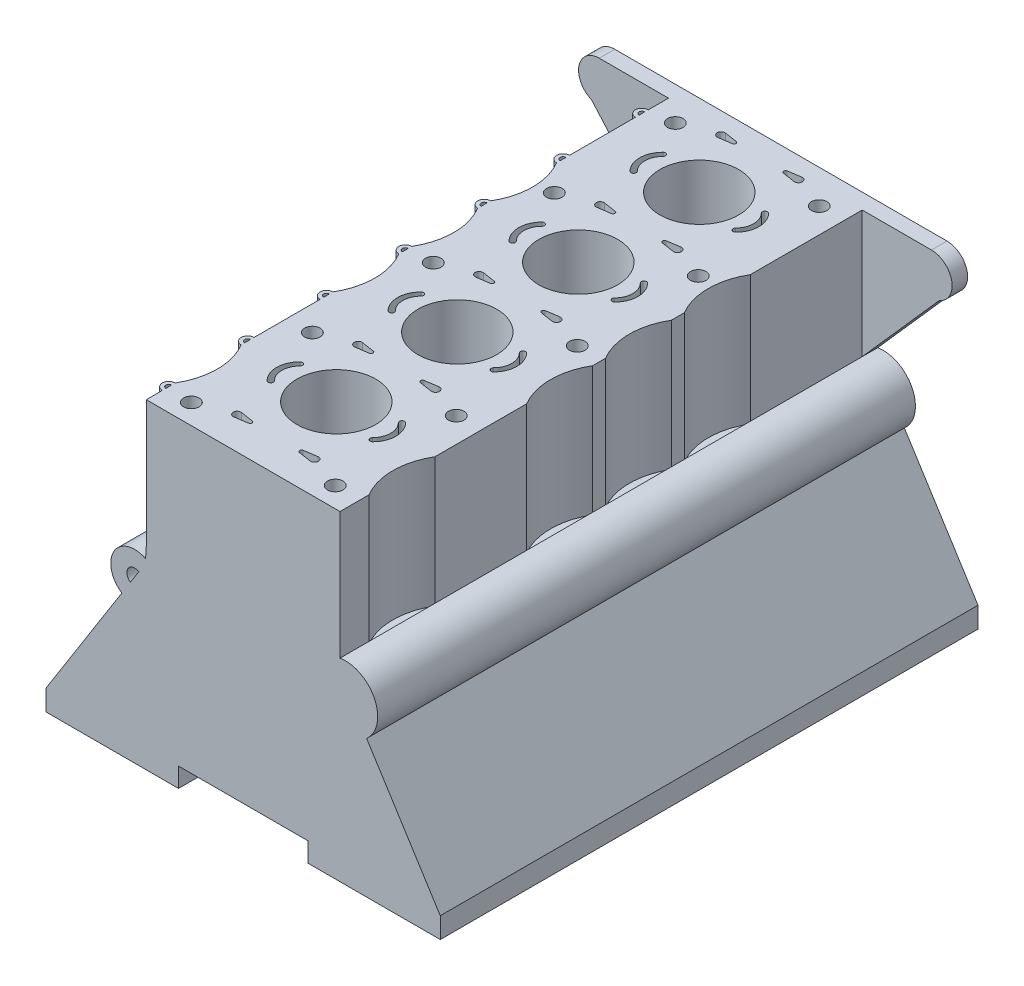
SolidWorks part; units mm, degrees
ref_plane "Front Plane" through (0, 0, 0) normal (0, 0, 1) x (1, 0, 0)
ref_plane "Top Plane" through (0, 0, 0) normal (0, 1, 0) x (1, 0, 0)
ref_plane "Right Plane" through (0, 0, 0) normal (1, 0, 0) x (0, 0, -1)
sketch "Sketch1" plane through (0, 0, 0) normal (0, 0, 1) x (1, 0, 0)
  line L0 (0, 162.6607) -> (0, -85.2855) construction
  line L1 (128.5, 162.6607) -> (-128.5, 162.6607)
  line L2 (-134.5607, 131.853) -> (-74.9405, 64.4333)
  line L3 (134.5607, 131.853) -> (74.9405, 64.4333)
  line L4 (-74.9405, 64.4333) -> (-75.6758, 52.4558)
  line L5 (74.9405, 64.4333) -> (75.6758, 52.4558)
  line L6 (-75.6758, 52.4558) -> (-152.5, -69.3393)
  line L7 (75.6758, 52.4558) -> (152.5, -69.3393)
  line L8 (-152.5, -69.3393) -> (-152.5, -85.3393)
  line L9 (152.5, -69.3393) -> (152.5, -85.3393)
  line L10 (-152.5, -85.3393) -> (152.5, -85.3393)
  arc A0 (-128.5, 162.6607) -> (-134.5607, 131.853) centre (-128.5, 146.6607) ccw
  arc A1 (128.5, 162.6607) -> (134.5607, 131.853) centre (128.5, 146.6607) cw
  point P17 (0, -85.2855)
  point P18 (0, -85.2855)
  dimension "D6" = 16
  dimension "D1" = 305
  dimension "D2" = 257
  dimension "D3" = 248
  dimension "D4" = 12
  dimension "D5" = 16
  dimension "D7" = 90
  dimension "D8" = 144
  dimension "D9" = 225
extrude "Boss-Extrude1" add sketch "Sketch1" along normal blind 12
sketch "Sketch2" plane through (0, 0, 12) normal (0, 0, 1) x (1, 0, 0)
  line L0 (-74.9405, 64.4333) -> (-74.9405, 162.6607)
  line L1 (74.9405, 64.4333) -> (74.9405, 162.6607)
  line L10 (-134.5607, 131.853) -> (-74.9405, 64.4333)
  line L11 (-74.9405, 64.4333) -> (-75.6758, 52.4558)
  line L12 (-75.6758, 52.4558) -> (-152.5, -69.3393)
  line L13 (-152.5, -69.3393) -> (-152.5, -85.3393)
  line L14 (-152.5, -85.3393) -> (152.5, -85.3393)
  line L15 (152.5, -85.3393) -> (152.5, -69.3393)
  line L16 (152.5, -69.3393) -> (75.6758, 52.4558)
  line L17 (75.6758, 52.4558) -> (74.9405, 64.4333)
  line L18 (74.9405, 64.4333) -> (134.5607, 131.853)
  line L19 (128.5, 162.6607) -> (-128.5, 162.6607)
  line L21 (-74.9405, 64.4333) -> (-75.6758, 52.4558)
  line L22 (-75.6758, 52.4558) -> (-152.5, -69.3393)
  line L23 (-152.5, -69.3393) -> (-152.5, -85.3393)
  line L24 (-152.5, -85.3393) -> (152.5, -85.3393)
  line L25 (152.5, -85.3393) -> (152.5, -69.3393)
  line L26 (152.5, -69.3393) -> (75.6758, 52.4558)
  line L27 (75.6758, 52.4558) -> (74.9405, 64.4333)
  line L29 (74.9405, 162.6607) -> (-74.9405, 162.6607)
  arc A2 (-128.5, 162.6607) -> (-134.5607, 131.853) centre (-128.5, 146.6607) ccw
  arc A3 (134.5607, 131.853) -> (128.5, 162.6607) centre (128.5, 146.6607) ccw
  dimension "D1" = 0
extrude "Boss-Extrude2" add sketch "Sketch2" along normal blind 404
sketch "Sketch3" plane through (0, 162.6607, 0) normal (0, 1, 0) x (1, 0, 0)
  line L0 (0, 0) -> (0, -416) construction
  line L1 (128.5, 0) -> (-128.5, 0) construction
  line L2 (74.9405, -416) -> (-74.9405, -416) construction
  line L3 (-134.6595, -63.1) -> (46.367, -63.1) construction
  line L4 (-75.6758, -416) -> (-75.6758, 0) construction
  line L5 (-74.9405, -416) -> (-74.9405, -12) construction
  line L6 (-29.9405, -203.5) -> (-25.1463, -203.5) construction
  line L7 (-29.4905, -200.5339) -> (-19.7155, -202.017)
  line L8 (-29.4905, -206.4661) -> (-19.7155, -204.983)
  line L9 (-18.4405, -203.5) -> (31.5571, -203.5) construction
  line L10 (29.4905, -206.4661) -> (19.7155, -204.983)
  line L11 (29.4905, -200.5339) -> (19.7155, -202.017)
  line L12 (-29.4905, -106.9339) -> (-19.7155, -108.417)
  line L13 (-29.4905, -112.8661) -> (-19.7155, -111.383)
  line L14 (29.4905, -112.8661) -> (19.7155, -111.383)
  line L15 (29.4905, -106.9339) -> (19.7155, -108.417)
  line L16 (-29.4905, -13.3339) -> (-19.7155, -14.817)
  line L17 (-29.4905, -19.2661) -> (-19.7155, -17.783)
  line L18 (29.4905, -19.2661) -> (19.7155, -17.783)
  line L19 (29.4905, -13.3339) -> (19.7155, -14.817)
  line L20 (-29.4905, -294.1339) -> (-19.7155, -295.617)
  line L21 (-29.4905, -300.0661) -> (-19.7155, -298.583)
  line L22 (29.4905, -300.0661) -> (19.7155, -298.583)
  line L23 (29.4905, -294.1339) -> (19.7155, -295.617)
  line L24 (-29.4905, -387.7339) -> (-19.7155, -389.217)
  line L25 (-29.4905, -393.6661) -> (-19.7155, -392.183)
  line L26 (29.4905, -393.6661) -> (19.7155, -392.183)
  line L27 (29.4905, -387.7339) -> (19.7155, -389.217)
  line L28 (-74.9405, -416) -> (-74.9405, -12) construction
  circle A0 centre (0, -63.1) radius 30.5
  circle A1 centre (-55.6758, -26) radius 6
  circle A2 centre (55.6758, -26) radius 6
  arc A3 (-39.46, -74.4137) -> (-39.46, -51.7863) centre (-28.1463, -63.1) cw construction
  arc A4 (-40.8742, -50.3721) -> (-40.8742, -75.8279) centre (-28.1463, -63.1) ccw
  arc A5 (-38.0458, -53.2005) -> (-38.0458, -72.9995) centre (-28.1463, -63.1) ccw
  arc A6 (-38.0458, -53.2005) -> (-40.8742, -50.3721) centre (-39.46, -51.7863) ccw
  arc A7 (-40.8742, -75.8279) -> (-38.0458, -72.9995) centre (-39.46, -74.4137) ccw
  arc A8 (39.46, -74.4137) -> (39.46, -51.7863) centre (28.1463, -63.1) ccw construction
  arc A9 (40.8742, -50.3721) -> (40.8742, -75.8279) centre (28.1463, -63.1) cw
  arc A10 (38.0458, -53.2005) -> (38.0458, -72.9995) centre (28.1463, -63.1) cw
  arc A11 (38.0458, -53.2005) -> (40.8742, -50.3721) centre (39.46, -51.7863) cw
  arc A12 (40.8742, -75.8279) -> (38.0458, -72.9995) centre (39.46, -74.4137) cw
  circle A13 centre (0, -156.7) radius 30.5
  circle A14 centre (55.6758, -119.6) radius 6
  circle A15 centre (-55.6758, -119.6) radius 6
  arc A16 (-39.46, -168.0137) -> (-39.46, -145.3863) centre (-28.1463, -156.7) cw construction
  arc A17 (-40.8742, -143.9721) -> (-40.8742, -169.4279) centre (-28.1463, -156.7) ccw
  arc A18 (-38.0458, -146.8005) -> (-38.0458, -166.5995) centre (-28.1463, -156.7) ccw
  arc A19 (-38.0458, -146.8005) -> (-40.8742, -143.9721) centre (-39.46, -145.3863) ccw
  arc A20 (-40.8742, -169.4279) -> (-38.0458, -166.5995) centre (-39.46, -168.0137) ccw
  arc A21 (39.46, -168.0137) -> (39.46, -145.3863) centre (28.1463, -156.7) ccw construction
  arc A22 (40.8742, -143.9721) -> (40.8742, -169.4279) centre (28.1463, -156.7) cw
  arc A23 (38.0458, -146.8005) -> (38.0458, -166.5995) centre (28.1463, -156.7) cw
  arc A24 (38.0458, -146.8005) -> (40.8742, -143.9721) centre (39.46, -145.3863) cw
  arc A25 (40.8742, -169.4279) -> (38.0458, -166.5995) centre (39.46, -168.0137) cw
  circle A26 centre (0, -250.3) radius 30.5
  circle A27 centre (55.6758, -213.2) radius 6
  circle A28 centre (-55.6758, -213.2) radius 6
  arc A29 (-39.46, -261.6137) -> (-39.46, -238.9863) centre (-28.1463, -250.3) cw construction
  arc A30 (-40.8742, -237.5721) -> (-40.8742, -263.0279) centre (-28.1463, -250.3) ccw
  arc A31 (-38.0458, -240.4005) -> (-38.0458, -260.1995) centre (-28.1463, -250.3) ccw
  arc A32 (-38.0458, -240.4005) -> (-40.8742, -237.5721) centre (-39.46, -238.9863) ccw
  arc A33 (-40.8742, -263.0279) -> (-38.0458, -260.1995) centre (-39.46, -261.6137) ccw
  arc A34 (39.46, -261.6137) -> (39.46, -238.9863) centre (28.1463, -250.3) ccw construction
  arc A35 (40.8742, -237.5721) -> (40.8742, -263.0279) centre (28.1463, -250.3) cw
  arc A36 (38.0458, -240.4005) -> (38.0458, -260.1995) centre (28.1463, -250.3) cw
  arc A37 (38.0458, -240.4005) -> (40.8742, -237.5721) centre (39.46, -238.9863) cw
  arc A38 (40.8742, -263.0279) -> (38.0458, -260.1995) centre (39.46, -261.6137) cw
  circle A39 centre (0, -343.9) radius 30.5
  circle A40 centre (55.6758, -306.8) radius 6
  circle A41 centre (-55.6758, -306.8) radius 6
  arc A42 (-39.46, -355.2137) -> (-39.46, -332.5863) centre (-28.1463, -343.9) cw construction
  arc A43 (-40.8742, -331.1721) -> (-40.8742, -356.6279) centre (-28.1463, -343.9) ccw
  arc A44 (-38.0458, -334.0005) -> (-38.0458, -353.7995) centre (-28.1463, -343.9) ccw
  arc A45 (-38.0458, -334.0005) -> (-40.8742, -331.1721) centre (-39.46, -332.5863) ccw
  arc A46 (-40.8742, -356.6279) -> (-38.0458, -353.7995) centre (-39.46, -355.2137) ccw
  arc A47 (39.46, -355.2137) -> (39.46, -332.5863) centre (28.1463, -343.9) ccw construction
  arc A48 (40.8742, -331.1721) -> (40.8742, -356.6279) centre (28.1463, -343.9) cw
  arc A49 (38.0458, -334.0005) -> (38.0458, -353.7995) centre (28.1463, -343.9) cw
  arc A50 (38.0458, -334.0005) -> (40.8742, -331.1721) centre (39.46, -332.5863) cw
  arc A51 (40.8742, -356.6279) -> (38.0458, -353.7995) centre (39.46, -355.2137) cw
  circle A52 centre (-55.6758, -400.4) radius 6
  circle A53 centre (55.6758, -400.4) radius 6
  arc A54 (-29.4905, -200.5339) -> (-29.4905, -206.4661) centre (-29.9405, -203.5) ccw
  arc A55 (-19.7155, -204.983) -> (-19.7155, -202.017) centre (-19.9405, -203.5) ccw
  arc A56 (29.4905, -200.5339) -> (29.4905, -206.4661) centre (29.9405, -203.5) cw
  arc A57 (19.7155, -204.983) -> (19.7155, -202.017) centre (19.9405, -203.5) cw
  arc A58 (-19.7155, -111.383) -> (-19.7155, -108.417) centre (-19.9405, -109.9) ccw
  arc A59 (-29.4905, -106.9339) -> (-29.4905, -112.8661) centre (-29.9405, -109.9) ccw
  arc A60 (19.7155, -111.383) -> (19.7155, -108.417) centre (19.9405, -109.9) cw
  arc A61 (29.4905, -106.9339) -> (29.4905, -112.8661) centre (29.9405, -109.9) cw
  arc A62 (-19.7155, -17.783) -> (-19.7155, -14.817) centre (-19.9405, -16.3) ccw
  arc A63 (-29.4905, -13.3339) -> (-29.4905, -19.2661) centre (-29.9405, -16.3) ccw
  arc A64 (19.7155, -17.783) -> (19.7155, -14.817) centre (19.9405, -16.3) cw
  arc A65 (29.4905, -13.3339) -> (29.4905, -19.2661) centre (29.9405, -16.3) cw
  arc A66 (-19.7155, -298.583) -> (-19.7155, -295.617) centre (-19.9405, -297.1) ccw
  arc A67 (-29.4905, -294.1339) -> (-29.4905, -300.0661) centre (-29.9405, -297.1) ccw
  arc A68 (19.7155, -298.583) -> (19.7155, -295.617) centre (19.9405, -297.1) cw
  arc A69 (29.4905, -294.1339) -> (29.4905, -300.0661) centre (29.9405, -297.1) cw
  arc A70 (-19.7155, -392.183) -> (-19.7155, -389.217) centre (-19.9405, -390.7) ccw
  arc A71 (-29.4905, -387.7339) -> (-29.4905, -393.6661) centre (-29.9405, -390.7) ccw
  arc A72 (19.7155, -392.183) -> (19.7155, -389.217) centre (19.9405, -390.7) cw
  arc A73 (29.4905, -387.7339) -> (29.4905, -393.6661) centre (29.9405, -390.7) cw
  point P19 (-44.1463, -63.1)
  point P32 (44.1463, -63.1)
  point P45 (-44.1463, -156.7)
  point P53 (44.1463, -156.7)
  point P67 (-44.1463, -250.3)
  point P75 (44.1463, -250.3)
  point P89 (-44.1463, -343.9)
  point P97 (44.1463, -343.9)
  point P171 (-18.4462, -203.0341)
  dimension "D1" = 61
  dimension "D3" = 12
  dimension "D6" = 18
  dimension "D7" = 2
  dimension "D12" = 6
  dimension "D13" = 3
  dimension "D18" = 93.6
  dimension "D2" = 63.1
  dimension "D4" = 20
  dimension "D5" = 26
  dimension "D8" = 30.7942
  dimension "D11" = 93.6
  dimension "D16" = 45
  dimension "D17" = 10
  dimension "D19" = 93.6
  dimension "D20" = 93.6
  dimension "D9" = 4
  dimension "D10" = 2
  dimension "D14" = 3
  dimension "D15" = 3
extrude "Cut-Extrude1" cut sketch "Sketch3" against normal blind 25
sketch "Sketch4" plane through (0, 162.6607, 0) normal (0, 1, 0) x (1, 0, 0)
  line L0 (-74.9405, -416) -> (-74.9405, -12) construction
  line L1 (-74.9405, -12) -> (-128.5, -12) construction
  circle A0 centre (-74.9405, -32.6) radius 2.25
  circle A1 centre (-74.9405, -32.6) radius 5
  circle A2 centre (-74.9405, -93.6) radius 5
  circle A3 centre (-74.9405, -93.6) radius 2.25
  circle A4 centre (-74.9405, -154.6) radius 5
  circle A5 centre (-74.9405, -154.6) radius 2.25
  circle A6 centre (-74.9405, -215.6) radius 5
  circle A7 centre (-74.9405, -215.6) radius 2.25
  circle A8 centre (-74.9405, -276.6) radius 5
  circle A9 centre (-74.9405, -276.6) radius 2.25
  circle A10 centre (-74.9405, -337.6) radius 5
  circle A11 centre (-74.9405, -337.6) radius 2.25
  circle A12 centre (-74.9405, -398.6) radius 5
  circle A13 centre (-74.9405, -398.6) radius 2.25
  dimension "D1" = 10
  dimension "D2" = 4.5
  dimension "D3" = 20.6
  dimension "D5" = 61
  dimension "D4" = 7
extrude "Boss-Extrude3" add sketch "Sketch4" against normal blind 100
sketch "Sketch5" plane through (0, 162.6607, 0) normal (0, 1, 0) x (1, 0, 0)
  line L0 (-74.9405, -342.6) -> (-74.9405, -393.6)
  line L1 (-74.9405, -220.6) -> (-74.9405, -271.6)
  line L3 (74.9405, -342.6) -> (74.9405, -393.6)
  line L4 (74.9405, -220.6) -> (74.9405, -271.6)
  line L5 (-74.9405, -159.6) -> (-74.9405, -210.6)
  line L6 (74.9405, -159.6) -> (74.9405, -210.6)
  line L7 (-74.9405, -98.6) -> (-74.9405, -149.6)
  line L8 (74.9405, -98.6) -> (74.9405, -149.6)
  arc A0 (-74.9405, -342.6) -> (-74.9405, -393.6) centre (-117.9492, -368.1) cw
  arc A1 (-74.9405, -220.6) -> (-74.9405, -271.6) centre (-117.9492, -246.1) cw
  arc A2 (74.9405, -342.6) -> (74.9405, -393.6) centre (117.9492, -368.1) ccw
  arc A3 (74.9405, -220.6) -> (74.9405, -271.6) centre (117.9492, -246.1) ccw
  arc A4 (-74.9405, -159.6) -> (-74.9405, -210.6) centre (-117.9492, -185.1) cw
  arc A5 (74.9405, -159.6) -> (74.9405, -210.6) centre (117.9492, -185.1) ccw
  arc A6 (-74.9405, -98.6) -> (-74.9405, -149.6) centre (-117.9492, -124.1) cw
  arc A7 (74.9405, -98.6) -> (74.9405, -149.6) centre (117.9492, -124.1) ccw
  dimension "D1" = 50
  dimension "D3" = 71
  dimension "D5" = 10
  dimension "D2" = 2
  dimension "D4" = 3
extrude "Cut-Extrude2" cut sketch "Sketch5" against normal blind 100
sketch "Sketch6" plane through (0, 0, 0) normal (0, 0, -1) x (-1, 0, 0)
  line L1 (72.5365, 100.6607) -> (25.7712, 100.6607)
  line L2 (25.7712, 100.6607) -> (2.3885, 60.1607)
  line L3 (2.3885, 60.1607) -> (25.7712, 19.6607)
  line L4 (25.7712, 19.6607) -> (72.5365, 19.6607)
  line L5 (72.5365, 19.6607) -> (95.9192, 60.1607)
  line L6 (95.9192, 60.1607) -> (72.5365, 100.6607)
  line L7 (-128.5, 162.6607) -> (128.5, 162.6607) construction
  line L9 (74.9405, 64.4333) -> (75.6758, 52.4558) construction
  circle A0 centre (49.1538, 60.1607) radius 40.5 construction
  dimension "D1" = 81
  dimension "D2" = 62
  dimension "D3" = 26
extrude "Boss-Extrude6" add sketch "Sketch6" against normal blind 12
sketch "Sketch9" plane through (0, 0, 0) normal (0, 0, -1) x (-1, 0, 0)
  line L0 (-128.5, 162.6607) -> (128.5, 162.6607) construction
  line L1 (-75.6758, 52.4558) -> (-74.9405, 64.4333) construction
  circle A0 centre (78.1774, 61.6607) radius 12.5
  circle A1 centre (78.1774, 61.6607) radius 5
  dimension "D1" = 25
  dimension "D2" = 10
  dimension "D3" = 101
  dimension "D4" = 153
extrude "Boss-Extrude7" add sketch "Sketch9" against normal blind 346
sketch "Sketch10" plane through (0, 0, 0) normal (0, 0, -1) x (-1, 0, 0)
  circle A1 centre (78.1774, 61.6607) radius 5
  circle A2 centre (78.1774, 61.6607) radius 5
  dimension "D1" = 0
extrude "Cut-Extrude5" cut sketch "Sketch10" against normal blind 346
sketch "Sketch12" plane through (0, 0, 0) normal (0, 0, -1) x (-1, 0, 0)
  circle A0 centre (83.9225, 39.3818) radius 18.5
  circle A1 centre (83.9225, 39.3818) radius 6
  dimension "D1" = 37
  dimension "D2" = 12
extrude "Boss-Extrude8" add sketch "Sketch12" against normal blind 150
ref_plane "Plane2" through (0, 78, 0) normal (0, 1, 0) x (1, 0, 0)
sketch "Sketch14" plane through (0, 78, 0) normal (0, 1, 0) x (1, 0, 0)
  line L0 (-74.9405, -12) -> (-128.5, -12) construction
  line L1 (-68.9405, -137) -> (-103.9405, -137)
  line L2 (-68.9405, -137) -> (-68.9405, -212)
  line L3 (-68.9405, -212) -> (-103.9405, -212)
  line L4 (-103.9405, -137) -> (-103.9405, -212)
  line L5 (-68.9405, -137) -> (-103.9405, -212) construction
  line L6 (-68.9405, -212) -> (-103.9405, -137) construction
  line L8 (-74.9405, -332.6) -> (-74.9405, -281.6) construction
  point P0 (-86.4405, -174.5)
  dimension "D1" = 75
  dimension "D2" = 35
  dimension "D3" = 125
  dimension "D4" = 29
extrude "Boss-Extrude10" add sketch "Sketch14" against normal blind 80
chamfer "Chamfer3" distance 24 angle 45 1 edges at (-103.9405, 78, 174.5)
sketch "Sketch16" plane through (0, 162.6607, 0) normal (0, 1, 0) x (1, 0, 0)
  circle A0 centre (0, -343.9) radius 30.5 construction
  circle A1 centre (0, -250.3) radius 30.5 construction
  circle A2 centre (0, -156.7) radius 30.5 construction
  circle A3 centre (0, -63.1) radius 30.5 construction
  circle A4 centre (0, -343.9) radius 30.5
  circle A5 centre (0, -250.3) radius 30.5
  circle A6 centre (0, -156.7) radius 30.5
  circle A7 centre (0, -63.1) radius 30.5
extrude "Cut-Extrude7" cut sketch "Sketch16" against normal through all
sketch "Sketch17" plane through (0, -85.3393, 0) normal (0, -1, 0) x (1, 0, 0)
  line L0 (-94, 124.7) -> (-94, 188.7)
  line L1 (-94, 31.1) -> (94, 31.1)
  line L2 (-94, 31.1) -> (-94, 95.1)
  line L3 (-94, 95.1) -> (94, 95.1)
  line L4 (94, 31.1) -> (94, 95.1)
  line L5 (-94, 31.1) -> (94, 95.1) construction
  line L6 (-94, 95.1) -> (94, 31.1) construction
  line L7 (-94, 124.7) -> (94, 124.7)
  line L8 (94, 124.7) -> (94, 188.7)
  line L9 (-94, 188.7) -> (94, 188.7)
  line L10 (-94, 218.3) -> (-94, 282.3)
  line L11 (-94, 218.3) -> (94, 218.3)
  line L12 (94, 218.3) -> (94, 282.3)
  line L13 (-94, 282.3) -> (94, 282.3)
  line L14 (-94, 311.9) -> (-94, 375.9)
  line L15 (-94, 311.9) -> (94, 311.9)
  line L16 (94, 311.9) -> (94, 375.9)
  line L17 (-94, 375.9) -> (94, 375.9)
  point P0 (0, 63.1)
  dimension "D1" = 64
  dimension "D2" = 188
  dimension "D4" = 125.6
  dimension "D3" = 4
extrude "Cut-Extrude8" cut sketch "Sketch17" against normal blind 130
sketch "Sketch18" plane through (0, 0, 0) normal (0, 0, -1) x (-1, 0, 0)
  circle A0 centre (83.9225, 39.3818) radius 18.5
  circle A1 centre (83.9225, 39.3818) radius 6
extrude "Boss-Extrude11" add sketch "Sketch18" against normal blind 216 from offset 200 offset against normal yes
sketch "Sketch19" plane through (0, 0, 416) normal (0, 0, 1) x (1, 0, 0)
  line L0 (152.5, -69.3393) -> (75.6758, 52.4558) construction
  line L1 (74.9405, 64.4333) -> (75.6758, 52.4558)
  line L2 (75.6758, 52.4558) -> (95.5448, 20.9561)
  arc A0 (74.9405, 64.4333) -> (95.5448, 20.9561) centre (79.0939, 39.7807) cw
  dimension "D1" = 25
extrude "Boss-Extrude12" add sketch "Sketch19" against normal blind 416
sketch "Sketch20" plane through (0, 0, 416) normal (0, 0, 1) x (1, 0, 0)
  line L0 (-152.5, -85.3393) -> (152.5, -85.3393) construction
  line L1 (-50, -100.3393) -> (50, -100.3393)
  line L2 (-50, -100.3393) -> (-50, -70.3393)
  line L3 (-50, -70.3393) -> (50, -70.3393)
  line L4 (50, -100.3393) -> (50, -70.3393)
  line L5 (-50, -100.3393) -> (50, -70.3393) construction
  line L6 (-50, -70.3393) -> (50, -100.3393) construction
  point P0 (0, -85.3393)
  dimension "D1" = 100
  dimension "D2" = 30
extrude "Cut-Extrude9" cut sketch "Sketch20" against normal through all
